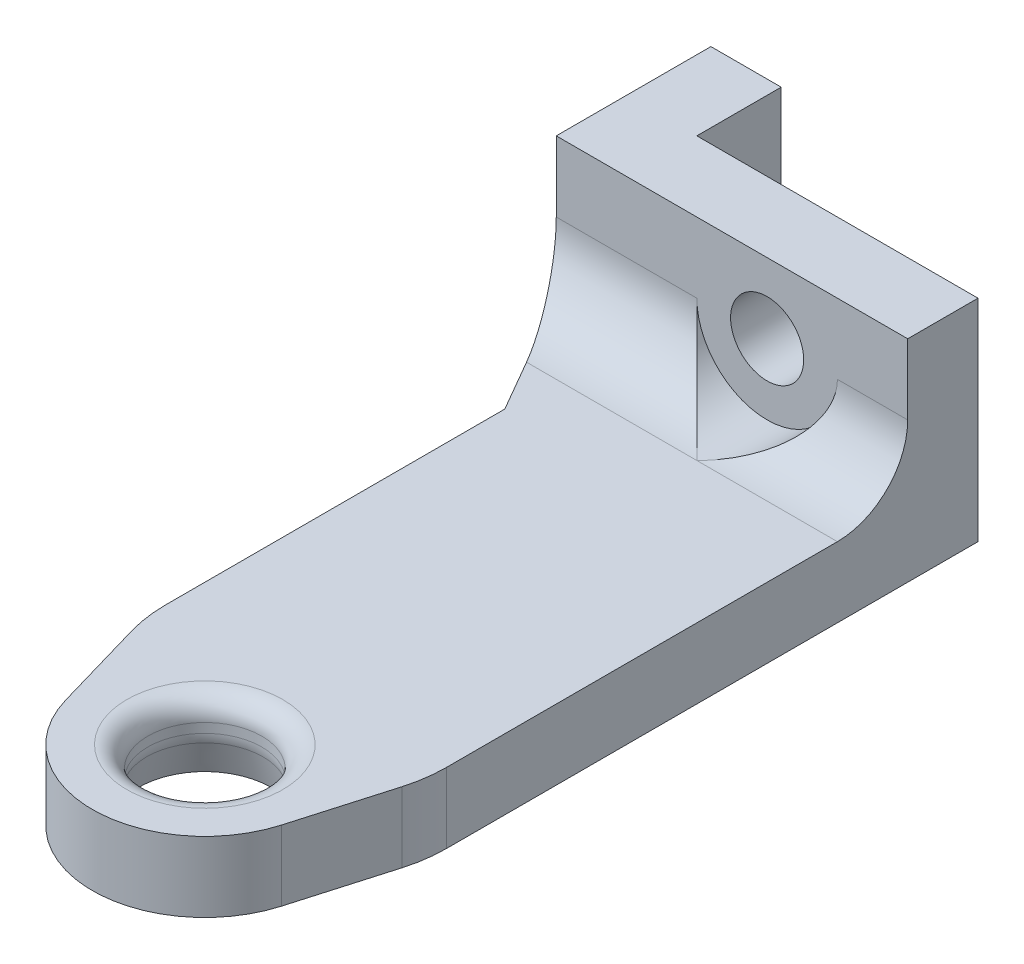
SolidWorks part; units mm, degrees
ref_plane "Front" through (0, 0, 0) normal (0, 0, 1) x (1, 0, 0)
ref_plane "Top" through (0, 0, 0) normal (0, 1, 0) x (1, 0, 0)
ref_plane "Right" through (0, 0, 0) normal (1, 0, 0) x (0, 0, -1)
sketch "Sketch1" plane through (0, 0, 0) normal (0, 1, 0) x (1, 0, 0)
  line L0 (0, 55) -> (0, 0) construction
  line L1 (-10, 45) -> (10, 45)
  line L2 (-10, 45) -> (-10, 65)
  line L3 (-10, 65) -> (10, 65)
  line L4 (10, 45) -> (10, 65)
  line L5 (-10, 45) -> (10, 65) construction
  line L6 (-10, 65) -> (10, 45) construction
  circle A0 centre (0, 0) radius 4
  point P3 (0, 55)
  dimension "D1" = 20
  dimension "D3" = 8
  dimension "D2" = 45
sketch "Sketch2" plane through (0, 0, 0) normal (0, 1, 0) x (1, 0, 0)
  line L0 (-7.6846, -2.2241) -> (-10, 5.7759)
  line L1 (-10, 5.7759) -> (-10, 45)
  line L2 (-10, 45) -> (10, 45) construction
  line L4 (0, 55) -> (0, 0) construction
  line L5 (0, 55) -> (0, 0) construction
  line L6 (10, 5.7759) -> (10, 45)
  line L7 (7.6846, -2.2241) -> (10, 5.7759)
  line L8 (-10, 45) -> (10, 45)
  circle A0 centre (0, 0) radius 8 construction
  circle A1 centre (0, 0) radius 4 construction
  arc A2 (7.6846, -2.2241) -> (-7.6846, -2.2241) centre (0, 0) cw
  circle A3 centre (0, 0) radius 4.05
  dimension "D1" = 4
  dimension "D2" = 8
  dimension "D3" = 8.1
extrude "Boss-Extrude1" add sketch "Sketch2" along normal blind 5
fillet "Fillet1" radius 10 2 edges at (10, 2.5, -5.7759) (-10, 2.5, -5.7759)
sketch "Sketch3" plane through (0, 0, -45) normal (0, 0, -1) x (-1, 0, 0)
  line L0 (10, 5) -> (10, 0) construction
  line L1 (-10, 0) -> (10, 0)
  line L2 (-10, 0) -> (-10, 15)
  line L3 (-10, 15) -> (10, 15)
  line L4 (10, 0) -> (10, 15)
  line L5 (-10, 5) -> (10, 5) construction
  dimension "D1" = 10
extrude "Boss-Extrude2" add sketch "Sketch3" against normal blind 5
sketch "Sketch6" plane through (0, 0, -40) normal (0, 0, 1) x (1, 0, 0)
  line L0 (0, 15) -> (0, 10) construction
  line L1 (-10, 15) -> (10, 15) construction
  line L2 (0, 10) -> (0, 5) construction
  line L3 (7.6846, 5) -> (-7.6846, 5) construction
  circle A0 centre (0, 10) radius 2.6
  dimension "D1" = 5.2
extrude "Cut-Extrude1" cut sketch "Sketch6" against normal through all
sketch "Sketch4" plane through (-10, 0, 0) normal (-1, 0, 0) x (0, 0, 1)
  line L0 (-40, 15) -> (-45, 15) construction
  line L1 (-40, 15) -> (-51, 15)
  line L2 (-40, 15) -> (-40, 0)
  line L3 (-40, 0) -> (-51, 0)
  line L4 (-51, 15) -> (-51, 0)
  line L5 (-40, 5) -> (-40, 15) construction
  line L6 (-45, 0) -> (-7.1939, 0) construction
  line L7 (-45, 15) -> (-45, 0) construction
  dimension "D1" = 6
extrude "Boss-Extrude3" add sketch "Sketch4" along normal blind 5
chamfer "Chamfer1" distance 5 angle 60 1 edges at (-10, 2.5, -40) first distance on face at (2.6, 10, -40)
fillet "Fillet2" radius 5 1 edges at (-2.5, 5, -40)
sketch "Sketch7" plane through (0, 0, -40) normal (0, 0, 1) x (1, 0, 0)
  circle A0 centre (0, 10) radius 5
  dimension "D1" = 10
extrude "Cut-Extrude3" cut sketch "Sketch7" along normal through all
chamfer "Chamfer2" distance 2.5 angle 15 1 edges at (0, 0, 4.05) first distance on face at (0, 5, 4.05)
fillet "Fillet3" radius 2.5 1 edges at (0, 2.5, -4.05)
fillet "Fillet4" radius 1.5 1 edges at (0, 5, 4.05)
sketch "Sketch8" plane through (-10, 10, 0) normal (1, 0, 0) x (0, 1, 0)
  line L0 (-9.4, -31.3397) -> (-9.4, -7.1939) construction
  line L2 (-5, -31.3397) -> (-10, -31.3397) construction
  line L3 (-10, -7.1939) -> (-5, -7.1939) construction
  line L5 (-10, -31.3397) -> (-10, -7.1939) construction
  text T0 "BLR-03\r\n" font "Century Gothic" height in points 14
  point P2 (0, 0)
  point P3 (-9.083, -31.3397)
  point P4 (0, 0)
  point P8 (-8.8806, -7.1939)
  dimension "D1" = 0.6
extrude "Part Num" cut sketch "Sketch8" along normal blind 0.4
